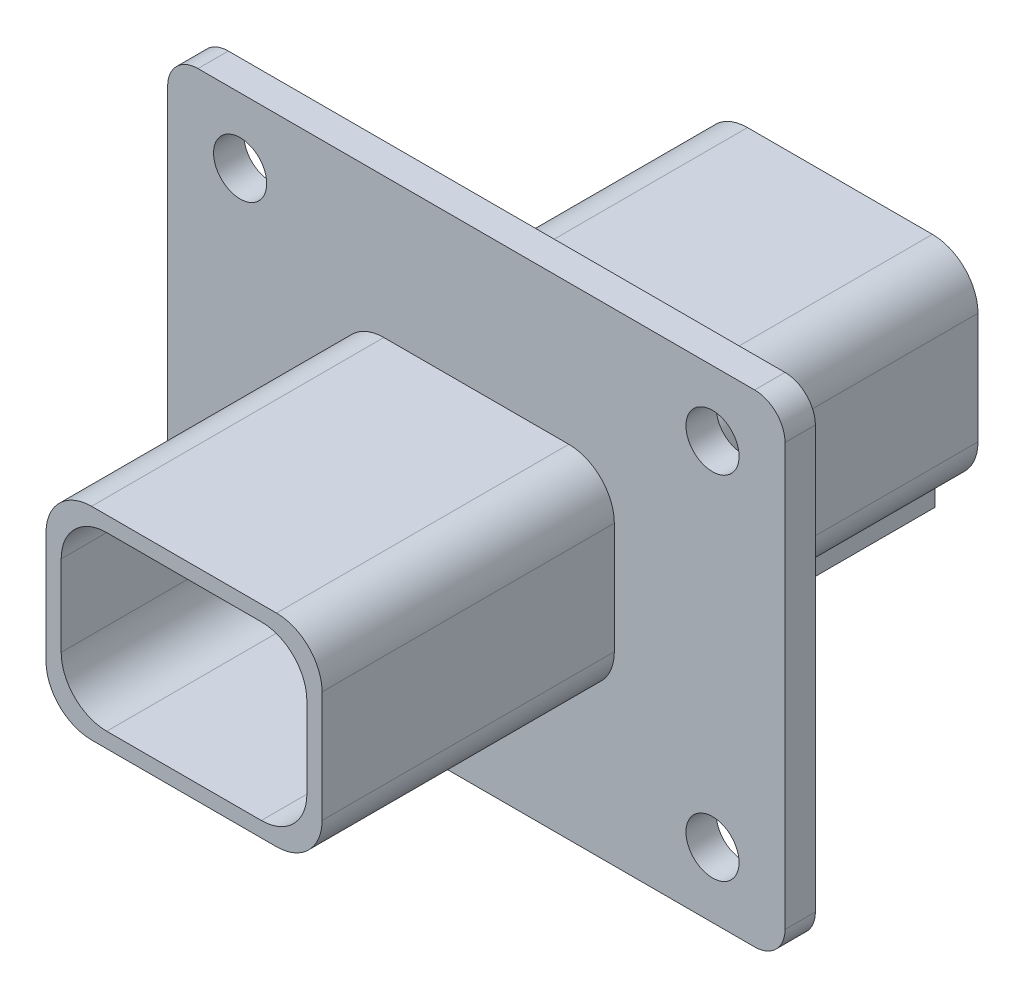
SolidWorks part; units mm, degrees
ref_plane "Front Plane" through (0, 0, 0) normal (0, 0, 1) x (1, 0, 0)
ref_plane "Top Plane" through (0, 0, 0) normal (0, 1, 0) x (1, 0, 0)
ref_plane "Right Plane" through (0, 0, 0) normal (1, 0, 0) x (0, 0, -1)
sketch "Sketch1" plane through (0, 0, 0) normal (0, 0, 1) x (1, 0, 0)
  line L0 (0, 0) -> (0, -15.885) construction
  line L1 (20.33, -15.885) -> (-20.33, -15.885)
  line L2 (20.33, -15.885) -> (20.33, 15.885)
  line L3 (20.33, 15.885) -> (-20.33, 15.885)
  line L4 (-20.33, -15.885) -> (-20.33, 15.885)
  line L5 (20.33, -15.885) -> (-20.33, 15.885) construction
  line L6 (20.33, 15.885) -> (-20.33, -15.885) construction
  line L7 (15.555, -11.585) -> (-15.555, -11.585) construction
  line L8 (15.555, -11.585) -> (15.555, 11.585) construction
  line L9 (15.555, 11.585) -> (-15.555, 11.585) construction
  line L10 (-15.555, -11.585) -> (-15.555, 11.585) construction
  line L11 (15.555, -11.585) -> (-15.555, 11.585) construction
  line L12 (15.555, 11.585) -> (-15.555, -11.585) construction
  line L13 (9.09, -6.665) -> (-9.09, -6.665) construction
  line L14 (9.09, -6.665) -> (9.09, 6.665) construction
  line L15 (9.09, 6.665) -> (-9.09, 6.665) construction
  line L16 (-9.09, -6.665) -> (-9.09, 6.665) construction
  line L17 (9.09, -6.665) -> (-9.09, 6.665) construction
  line L18 (9.09, 6.665) -> (-9.09, -6.665) construction
  line L20 (6.245, -8.835) -> (-6.245, -8.835) construction
  line L21 (6.245, -8.835) -> (6.245, -6.665) construction
  line L22 (6.245, -6.665) -> (-6.245, -6.665) construction
  line L23 (-6.245, -8.835) -> (-6.245, -6.665) construction
  line L24 (6.245, -8.835) -> (-6.245, -6.665) construction
  line L25 (6.245, -6.665) -> (-6.245, -8.835) construction
  circle A0 centre (-15.555, 11.585) radius 1.75
  circle A1 centre (-15.555, -11.585) radius 1.75
  circle A2 centre (15.555, -11.585) radius 1.75
  circle A3 centre (15.555, 11.585) radius 1.75
  point P0 (0, 0)
  point P6 (0, 0)
  point P15 (0, 0)
  point P22 (0, -7.75)
  point P27 (0, 0)
  dimension "D1" = 3.5
  dimension "D2" = 31.11
  dimension "D3" = 23.17
  dimension "D4" = 31.77
  dimension "D5" = 40.66
  dimension "D6" = 18.18
  dimension "D7" = 13.33
  dimension "D8" = 2.17
  dimension "D9" = 12.49
extrude "Boss-Extrude1" add sketch "Sketch1" along normal blind 2
sketch "Sketch2" plane through (0, 0, 0) normal (0, 0, -1) x (-1, 0, 0)
  line L0 (6.245, -6.665) -> (9.09, -6.665)
  line L1 (-9.09, 6.665) -> (9.09, 6.665)
  line L2 (-9.09, 6.665) -> (-9.09, -6.665)
  line L3 (-9.09, -6.665) -> (-6.245, -6.665)
  line L4 (9.09, 6.665) -> (9.09, -6.665)
  line L6 (-6.245, -6.665) -> (-6.245, -8.835)
  line L7 (-6.245, -8.835) -> (6.245, -8.835)
  line L8 (6.245, -6.665) -> (6.245, -8.835)
  line L9 (8.09, -5.665) -> (-8.09, -5.665)
  line L10 (8.09, -5.665) -> (8.09, 5.665)
  line L11 (8.09, 5.665) -> (-8.09, 5.665)
  line L12 (-8.09, -5.665) -> (-8.09, 5.665)
  line L13 (8.09, -5.665) -> (-8.09, 5.665) construction
  line L14 (8.09, 5.665) -> (-8.09, -5.665) construction
  point P12 (0, 0)
  dimension "D1" = 1
  dimension "D2" = 1
extrude "Boss-Extrude2" add sketch "Sketch2" along normal blind 21.95
sketch "Sketch3" plane through (0, 0, 2) normal (0, 0, 1) x (1, 0, 0)
  line L1 (-9.09, 6.665) -> (9.09, 6.665)
  line L2 (-9.09, 6.665) -> (-9.09, -6.665)
  line L3 (-9.09, -6.665) -> (9.09, -6.665)
  line L4 (9.09, 6.665) -> (9.09, -6.665)
  line L5 (8.09, -5.665) -> (-8.09, -5.665)
  line L6 (8.09, -5.665) -> (8.09, 5.665)
  line L7 (8.09, 5.665) -> (-8.09, 5.665)
  line L8 (-8.09, -5.665) -> (-8.09, 5.665)
  line L9 (8.09, -5.665) -> (-8.09, 5.665) construction
  line L10 (8.09, 5.665) -> (-8.09, -5.665) construction
  point P7 (0, 0)
  dimension "D1" = 1
  dimension "D2" = 1
extrude "Boss-Extrude3" add sketch "Sketch3" along normal blind 19.25
fillet "Fillet2" radius 3 16 edges at (-8.09, -5.665, -10.975) (-8.09, 5.665, -10.975) (8.09, -5.665, -10.975) (8.09, 5.665, -10.975) (-9.09, -6.665, -10.975) (9.09, -6.665, -10.975) (-9.09, 6.665, -10.975) (9.09, 6.665, -10.975) (-8.09, 5.665, 11.625) (-8.09, -5.665, 11.625) (8.09, 5.665, 11.625) (8.09, -5.665, 11.625) (-9.09, 6.665, 11.625) (-9.09, -6.665, 11.625) (9.09, -6.665, 11.625) (9.09, 6.665, 11.625)
fillet "Fillet3" radius 2 4 edges at (-20.33, 15.885, 1) (-20.33, -15.885, 1) (20.33, -15.885, 1) (20.33, 15.885, 1)
